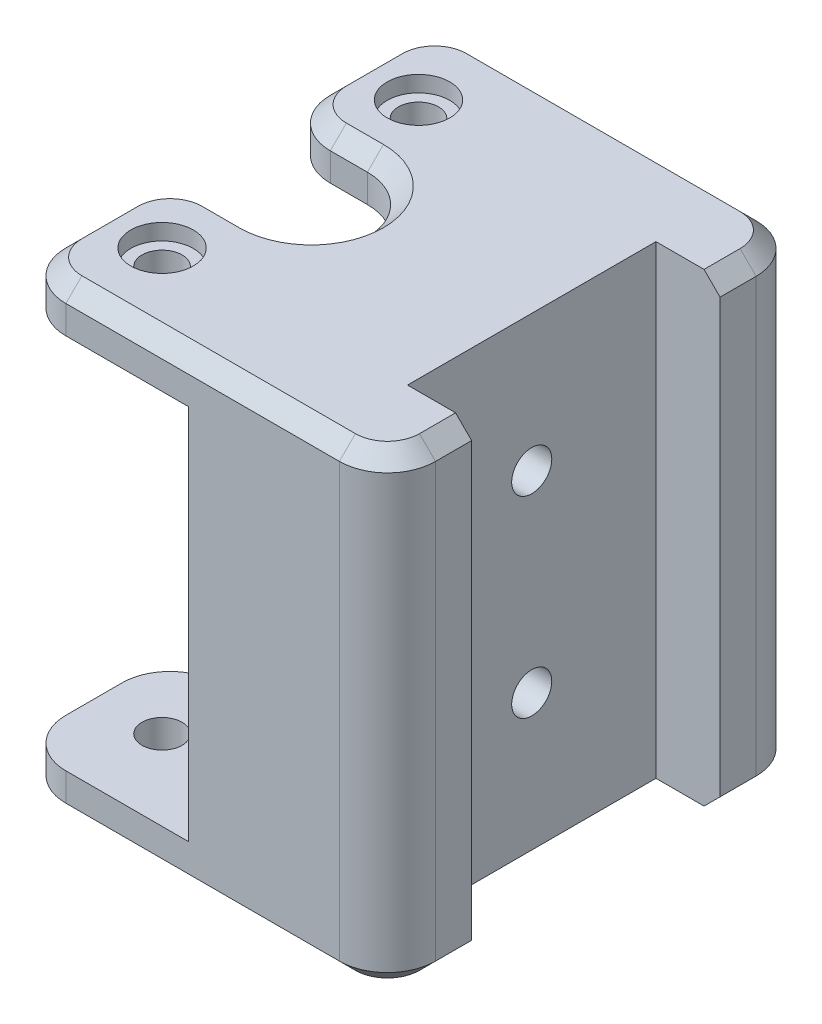
SolidWorks part; units mm, degrees
ref_plane "Спереди" through (0, 0, 0) normal (0, 0, 1) x (1, 0, 0)
ref_plane "Сверху" through (0, 0, 0) normal (0, 1, 0) x (1, 0, 0)
ref_plane "Справа" through (0, 0, 0) normal (1, 0, 0) x (0, 0, -1)
sketch "Эскиз2" plane through (0, 0, 0) normal (0, 1, 0) x (1, 0, 0)
  line L0 (23.6854, 8) -> (23.6854, -8) construction
  line L2 (19.6854, 13) -> (42.75, 13)
  line L3 (19.6854, 13) -> (19.6854, -13)
  line L4 (19.6854, -13) -> (42.75, -13)
  line L5 (42.75, 13) -> (42.75, -13)
  line L6 (19.6854, 13) -> (42.75, -13) construction
  line L7 (19.6854, -13) -> (42.75, 13) construction
  circle A0 centre (0, 0) radius 25 construction
  circle A1 centre (23.6854, 8) radius 1.25
  circle A2 centre (23.6854, -8) radius 1.25
  point P7 (31.2177, 0)
  dimension "D1" = 50
  dimension "D3" = 2.5
  dimension "D4" = 2.5
  dimension "D2" = 16
  dimension "D5" = 4
  dimension "D6" = 42.75
  dimension "D7" = 26
extrude "Бобышка-Вытянуть1" add sketch "Эскиз2" along normal mid plane 29
sketch "Эскиз3" plane through (0, 0, 0) normal (0, 1, 0) x (1, 0, 0)
  circle A0 centre (0, 0) radius 33
  dimension "D1" = 66
extrude "Вырез-Вытянуть1" cut sketch "Эскиз3" against normal mid plane 23.5
sketch "Эскиз4" plane through (0, 14.5, 0) normal (0, 1, 0) x (1, 0, 0)
  line L0 (25, 3.5) -> (19.6854, 3.5)
  line L1 (19.6854, 13) -> (19.6854, -13) construction
  line L2 (19.6854, 3.5) -> (19.6854, -3.5)
  line L3 (19.6854, -3.5) -> (25, -3.5)
  circle A0 centre (0, 0) radius 25 construction
  circle A1 centre (25, 0) radius 3.5
  line M6 (19.6854, 13) -> (19.6854, -13)
  dimension "D1" = 7
extrude "Вырез-Вытянуть2" cut sketch "Эскиз4" against normal through all contours A1 | A1 L0 L3 M6 region at (21.0872, 14.5, 0) region at (25, 14.5, 0)
sketch "Эскиз5" plane through (42.75, 0, 0) normal (1, 0, 0) x (0, 0, -1)
  line L0 (-13, -14.5) -> (13, -14.5) construction
  line L1 (-7.75, 14.5) -> (7.75, 14.5)
  line L2 (-7.75, 14.5) -> (-7.75, -14.5)
  line L3 (-7.75, -14.5) -> (7.75, -14.5)
  line L4 (7.75, 14.5) -> (7.75, -14.5)
  line L5 (-7.75, 14.5) -> (7.75, -14.5) construction
  line L6 (-7.75, -14.5) -> (7.75, 14.5) construction
  point P0 (0, 0)
  dimension "D1" = 15.5
extrude "Вырез-Вытянуть3" cut sketch "Эскиз5" against normal blind 4
fillet "Скругление1" radius 3 10 edges at (42.75, 0, -13) (19.6854, -13.125, -13) (19.6854, -13.125, -3.5) (19.6854, -13.125, 3.5) (19.6854, -13.125, 13) (19.6854, 13.125, -13) (19.6854, 13.125, -3.5) (19.6854, 13.125, 3.5) (19.6854, 13.125, 13) (42.75, 0, 13)
sketch "Эскиз6" plane through (38.75, 0, 0) normal (1, 0, 0) x (0, 0, -1)
  line L0 (-7.75, 0) -> (7.75, 0) construction
  line L1 (-7.75, 14.5) -> (-7.75, -14.5) construction
  line L2 (7.75, -14.5) -> (7.75, 14.5) construction
  circle A0 centre (0, 6) radius 1.25
  circle A1 centre (0, -6) radius 1.25
  point P12 (0, 0)
  dimension "D2" = 2.5
  dimension "D1" = 12
extrude "Вырез-Вытянуть4" cut sketch "Эскиз6" against normal through all
chamfer "Фаска1" distance 1 angle 45 30 edges at (42.75, -14.5, -8.875) (41.8713, -14.5, -12.1213) (31.2177, -14.5, -13) (20.5641, -14.5, -12.1213) (19.6854, -14.5, -8.25) (20.5641, -14.5, -4.3787) (23.8427, -14.5, -3.5) (28.5, -14.5, 0) (23.8427, -14.5, 3.5) (20.5641, -14.5, 4.3787) (19.6854, -14.5, 8.25) (42.75, -14.5, 8.875) (20.5641, -14.5, 12.1213) (41.8713, -14.5, 12.1213) (31.2177, -14.5, 13) (42.75, 14.5, -8.875) (41.8713, 14.5, -12.1213) (31.2177, 14.5, -13) (20.5641, 14.5, -12.1213) (19.6854, 14.5, -8.25) (20.5641, 14.5, -4.3787) (23.8427, 14.5, -3.5) (28.5, 14.5, 0) (23.8427, 14.5, 3.5) (20.5641, 14.5, 4.3787) (19.6854, 14.5, 8.25) (42.75, 14.5, 8.875) (20.5641, 14.5, 12.1213) (41.8713, 14.5, 12.1213) (31.2177, 14.5, 13)
sketch "Эскиз7" plane through (0, 14.5, 0) normal (0, 1, 0) x (1, 0, 0)
  circle A0 centre (23.6854, 8) radius 1.95
  circle A1 centre (23.6854, -8) radius 1.95
  dimension "D1" = 3.9
  dimension "D2" = 3.9
extrude "Вырез-Вытянуть5" cut sketch "Эскиз7" against normal blind 1
mirror "Зеркальное отражение1" about plane through (0, 0, 0) normal (0, 1, 0) of "Вырез-Вытянуть5"
sketch "Эскиз8" plane through (0, 0, 0) normal (1, 0, 0) x (0, 0, -1)
  line L1 (1.1691, 3.975) -> (2.3383, 6)
  line L2 (2.3383, 6) -> (1.1691, 8.025)
  line L3 (1.1691, 8.025) -> (-1.1691, 8.025)
  line L4 (-1.1691, 8.025) -> (-2.3383, 6)
  line L5 (-2.3383, 6) -> (-1.1691, 3.975)
  line L6 (-1.1691, 3.975) -> (1.1691, 3.975)
  line L7 (1.1691, -8.025) -> (2.3383, -6)
  line L8 (2.3383, -6) -> (1.1691, -3.975)
  line L9 (1.1691, -3.975) -> (-1.1691, -3.975)
  line L10 (-1.1691, -3.975) -> (-2.3383, -6)
  line L11 (-2.3383, -6) -> (-1.1691, -8.025)
  line L12 (-1.1691, -8.025) -> (1.1691, -8.025)
  circle A0 centre (0, 6) radius 2.025 construction
  circle A1 centre (0, -6) radius 2.025 construction
  dimension "D1" = 4.05
  dimension "D2" = 4.05
extrude "Вырез-Вытянуть6" cut sketch "Эскиз8" along normal offset from surface (35.75 mm away) 3 up to face at (38.75, 6, -1.25)
equation "\"motor_diameter\"= 30"
equation "\"mm_diameter\"= IIF ( \"motor_diameter\" < 34 , 41 , \"motor_diameter\" + 8 )"
equation "\"upper_shafts_diameter\"= 5"
equation "\"upper_shats_length\"= 180"
equation "\"upper_bearing_d1\"= 10"
equation "\"upper_bearing_d2\"= 5"
equation "\"upper_bearing_h\"= 15"
equation "\"lower_shafts_diameter\"= 5"
equation "\"lower_shafts_length\"= 180"
equation "\"lower_bearing_d1\"= 10"
equation "\"lower_bearing_d2\"= 5"
equation "\"lower_bearing_h\"= 15"
equation "\"print_offset\"= 0.5"
equation "\"bh_screws_d\"= 2"
equation "\"bh_screws_h\"= 20"
equation "\"bh_screws_hh_d\"= 3.4"
equation "\"bh_screws_hh_h\"= 2"
equation "\"bh_nut_d\"= 3.8"
equation "\"bh_nut_h\"= 2"
equation "\"motor_screws_d\"= 3"
equation "\"motor_screws_h\"= 16"
equation "\"motor_screws_hh_d\"= 5.5"
equation "\"motor_screws_hh_h\"= 3"
equation "\"plate_hole_distance\"= 25.4"
equation "\"plate_screws_d\"= 6.5"
equation "\"shafts_diameter\"= IIF ( \"mm_diameter\" < 42 , 42 + 8 , \"mm_diameter\" + 8 )"
equation "\"central_hole_diameter\"= 8"
equation "\"bh_thikness\"= 4"
equation "\"ends_screws_d\"= 4"
equation "\"ends_screws_h\"= 16"
equation "\"ends_screws_hh_d\"= 6.7"
equation "\"ends_screws_hh_h\"= 4.1"
equation "\"ends_nut_d\"= 6.8"
equation "\"ends_nut_h\"= 3"
equation "\"system_radius\" = ( \"shafts_diameter\" + 12 + \"bh_thikness\" / 2 ) / 2"
equation "\"encoder_distance\"= \"system_radius\" + 4"
equation "\"tape_position\"= \"encoder_distance\" - 2 + 3.9 + 1.7 / 2"
equation "\"D1@Эскиз2\"=\"shafts_diameter\""
equation "\"D3@Эскиз2\"=\"bh_screws_d\"+\"print_offset\""
equation "\"D4@Эскиз2\"=\"D3@Эскиз2\""
equation "\"D5@Эскиз2\"=\"bh_thikness\""
equation "\"D6@Эскиз2\"=\"tape_position\"+4"
equation "\"D1@Бобышка-Вытянуть1\"=\"lower_bearing_h\"+\"bh_thikness\"*2+6"
equation "\"D1@Эскиз3\"=\"system_radius\"*2+2"
equation "\"D1@Вырез-Вытянуть1\"=\"lower_bearing_h\"+\"bh_thikness\"*2+\"print_offset\""
equation "\"D1@Эскиз4\"=\"lower_shafts_diameter\"+2"
equation "\"D1@Эскиз5\"=\"print_offset\"+15"
equation "\"D2@Эскиз6\"=\"bh_screws_d\"+\"print_offset\""
equation "\"D1@Эскиз7\"=\"bh_screws_hh_d\"+\"print_offset\""
equation "\"D2@Эскиз7\"=\"D1@Эскиз7\""
equation "\"D1@Эскиз8\"=\"bh_nut_d\"+\"print_offset\"/2"
equation "\"D2@Эскиз8\"=\"D1@Эскиз8\""
equation "\"ft_sensor_d1\" = 9.8"
equation "\"ft_sensor_d2\"= 24.9"
equation "\"ft_sensor_h\"= 7"
equation "\"carbon_pipe_d\"= 14"
